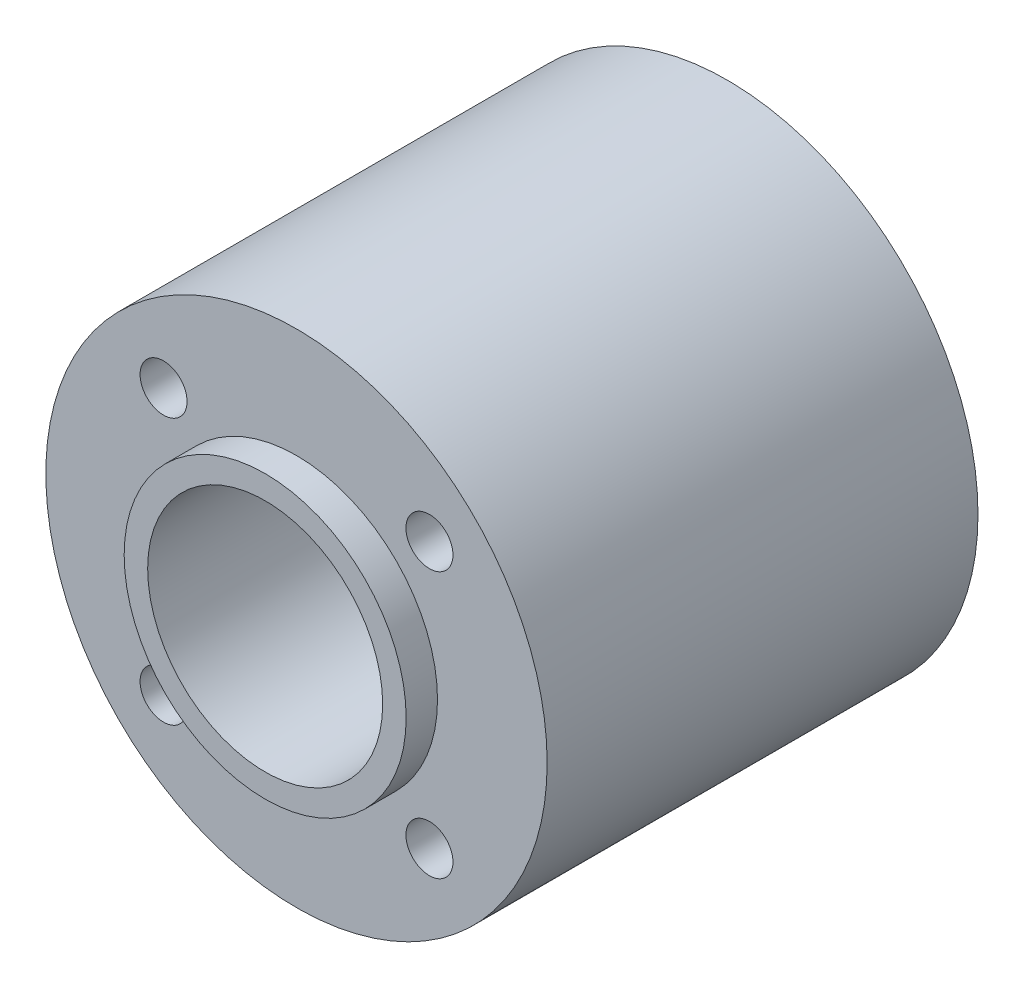
SolidWorks part; units mm, degrees
ref_plane "Front Plane" through (0, 0, 0) normal (0, 0, 1) x (1, 0, 0)
ref_plane "Top Plane" through (0, 0, 0) normal (0, 1, 0) x (1, 0, 0)
ref_plane "Right Plane" through (0, 0, 0) normal (1, 0, 0) x (0, 0, -1)
sketch "Sketch1" plane through (0, 0, 0) normal (0, 0, 1) x (1, 0, 0)
  circle A0 centre (0, 0) radius 32
  circle A1 centre (0, 0) radius 18
  circle A2 centre (0, 0) radius 15
  dimension "D1" = 64
  dimension "D2" = 36
  dimension "D3" = 30
extrude "Boss-Extrude1" add sketch "Sketch1" against normal blind 55 contours A0 A1 | A1 A2 region at (-31.0949, 0, 0) region at (-17.4909, 0, 0)
extrude "Boss-Extrude2" add sketch "Sketch1<3>" along normal blind 4 contours A1 A2 region at (-17.4909, 0, 0)
sketch "Sketch1<3>" plane through (0, 0, 0) normal (0, 0, 1) x (1, 0, 0) same geometry as "Sketch1"
extrude "Boss-Extrude4" add sketch "Sketch1<6>" against normal blind 4 from surface contours A1 A2 region at (-17.4909, 0, 0) starting at face at (32, 0, -55)
sketch "Sketch1<6>" plane through (0, 0, 0) normal (0, 0, 1) x (1, 0, 0) same geometry as "Sketch1"
sketch "Sketch2" plane through (0, 0, 0) normal (0, 0, 1) x (1, 0, 0)
  line L0 (0, 0) -> (0, 33.0698) construction
  line L1 (0, 0) -> (-16.9706, 16.9706) construction
  circle A0 centre (0, 0) radius 24
  circle A1 centre (-16.9706, 16.9706) radius 3
  circle A2 centre (16.9706, 16.9706) radius 3
  circle A3 centre (16.9706, -16.9706) radius 3
  circle A4 centre (-16.9706, -16.9706) radius 3
  circle A5 centre (0, 0) radius 18 construction
  dimension "D1" = 48
  dimension "D2" = 6
  dimension "D3" = 4
extrude "Cut-Extrude1" cut sketch "Sketch2" against normal blind 191 contours A0 A1 | A0 A1 | A0 A2 | A0 A2 | A0 A3 | A0 A3 | A0 A4 | A0 A4 region at (16.0468, 16.0468, 0) region at (17.8466, 17.8466, 0) region at (17.8466, -17.8466, 0) region at (16.0468, -16.0468, 0) region at (-16.0468, 16.0468, 0) region at (-17.8466, 17.8466, 0) region at (-17.8466, -17.8466, 0) region at (-16.0468, -16.0468, 0)
